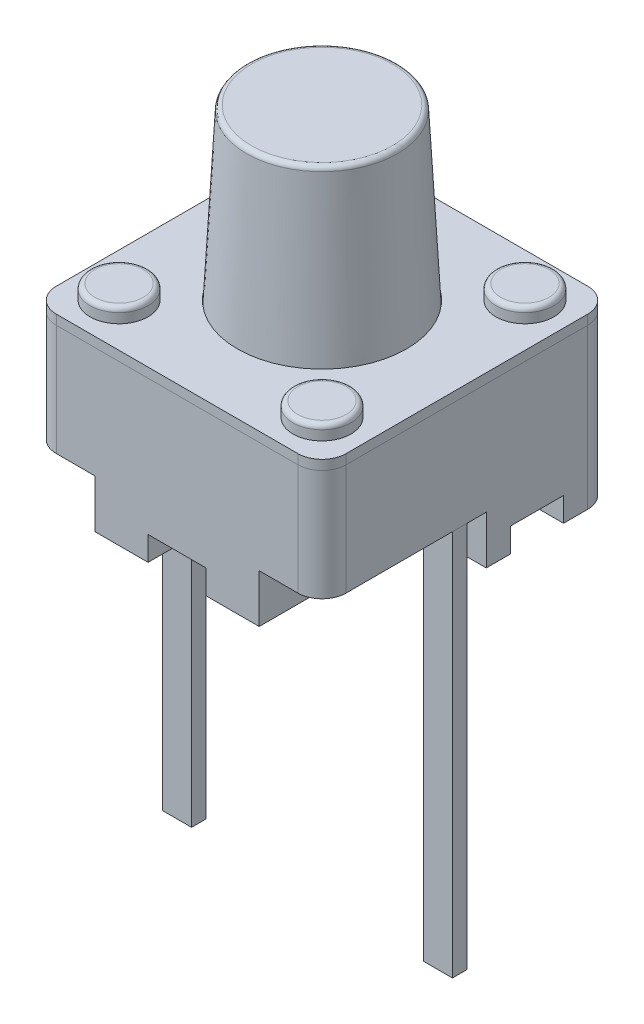
SolidWorks part; units mm, degrees
material "Custom Plastic"
ref_plane "Front Plane" through (0, 0, 0) normal (0, 0, 1) x (1, 0, 0)
ref_plane "Top Plane" through (0, 0, 0) normal (0, 1, 0) x (1, 0, 0)
ref_plane "Right Plane" through (0, 0, 0) normal (1, 0, 0) x (0, 0, -1)
sketch "Sketch1" plane through (0, 0, 0) normal (0, 1, 0) x (1, 0, 0)
  line L0 (-3.2652, 0) -> (3.207, 0) construction
  line L1 (-2.5, 3) -> (2.5, 3)
  line L2 (-3, 2.5) -> (-3, -2.5)
  line L3 (-2.5, -3) -> (2.5, -3)
  line L4 (3, 2.5) -> (3, -2.5)
  line L5 (-3, 3) -> (3, -3) construction
  line L6 (-3, -3) -> (3, 3) construction
  line L7 (0, -3.1905) -> (0, 3.2124) construction
  line L8 (3, 0) -> (2.4, 0)
  line L9 (3, 0) -> (3, -0.3)
  line L10 (3, -0.3) -> (2.4, -0.3)
  line L11 (2.4, 0) -> (2.4, -0.3)
  line L12 (-3, -0.3) -> (-2.4, -0.3)
  line L13 (-2.4, 0) -> (-2.4, -0.3)
  line L14 (-3, 0) -> (-2.4, 0)
  circle A0 centre (2.1, 2.1) radius 0.6
  circle A1 centre (2.1, -2.1) radius 0.6
  circle A2 centre (-2.1, -2.1) radius 0.6
  circle A3 centre (-2.1, 2.1) radius 0.6
  circle A4 centre (0, 0) radius 1.75
  arc A5 (2.5, 3) -> (3, 2.5) centre (2.5, 2.5) cw
  arc A6 (2.5, -3) -> (3, -2.5) centre (2.5, -2.5) ccw
  arc A7 (-3, -2.5) -> (-2.5, -3) centre (-2.5, -2.5) ccw
  arc A8 (-2.5, 3) -> (-3, 2.5) centre (-2.5, 2.5) ccw
  point P0 (0, 0)
  point P1 (0, 0)
  point P9 (0, 0)
  point P18 (0, 0)
  dimension "D1" = 6
  dimension "D2" = 0.9
  dimension "D3" = 1.2
  dimension "D5" = 3.5
  dimension "D6" = 0.5
  dimension "D7" = 0.6
  dimension "D8" = 0.3
  dimension "D4" = 4
extrude "Base" add sketch "Sketch1" along normal blind 3.3 contours L14 L2 L12 L13 | L1 A8 L2 L14 L13 L12 A7 L3 A6 L4 L10 L11 L8 A5 A0 A1 A2 A3 A4 | A3 | A2 | A4 | A1 | L8 L11 L10 L4 | A0 region at (0, 0, -2.9151) region at (-2.7, 0, 0.15) region at (2.7, 0, 0.15) region at (2.1, 0, -2.1) region at (2.1, 0, 2.1) region at (-2.1, 0, 2.1) region at (-2.1, 0, -2.1) region at (0, 0, 0)
extrude "Top Plate" add sketch "Sketch1<3>" along normal blind 0.2 from surface separate body contours L1 A8 L2 L14 L13 L12 A7 L3 A6 L4 L10 L11 L8 A5 A0 A1 A2 A3 A4 | L8 L11 L10 L4 | L14 L2 L12 L13 region at (0, 0, -2.9151) region at (-2.7, 0, 0.15) region at (2.7, 0, 0.15) starting at face at (0, 3.3, 0)
sketch "Sketch1<3>" plane through (0, 0, 0) normal (0, 1, 0) x (1, 0, 0) same geometry as "Sketch1"
extrude "Knobs" add sketch "Sketch1<4>" along normal blind 0.5 from offset 3.3 contours A1 | A2 | A3 | A0 region at (2.1, 0, -2.1) region at (2.1, 0, 2.1) region at (-2.1, 0, 2.1) region at (-2.1, 0, -2.1)
sketch "Sketch1<4>" plane through (0, 0, 0) normal (0, 1, 0) x (1, 0, 0) same geometry as "Sketch1"
extrude "Actuator" add sketch "Sketch1<5>" along normal blind 3.7 draft 3 from surface separate body contours A4 region at (0, 0, 0) starting at face at (-2.1, 3.3, -1.5)
sketch "Sketch1<5>" plane through (0, 0, 0) normal (0, 1, 0) x (1, 0, 0) same geometry as "Sketch1"
sketch "Sketch2" plane through (0, 0, 0) normal (0, -1, 0) x (1, 0, 0)
  line L0 (0, 3) -> (0.6, 3)
  line L1 (0, 3) -> (0, -3) construction
  line L2 (-2.5, 3) -> (2.5, 3) construction
  line L3 (0.6, 3) -> (1.7, 3)
  line L4 (0, -3) -> (0.6, -3)
  line L5 (-1.7, -2) -> (-3, -2)
  line L6 (0.6, -3) -> (0.6, 3)
  line L7 (-1.7, -0.9) -> (-1.7, -2)
  line L8 (-1.7, -0.9) -> (-3, -0.9)
  line L9 (1.7, -0.9) -> (3, -0.9)
  line L10 (1.7, -0.9) -> (1.7, -2)
  line L11 (-3, -0.4) -> (-1.7, -0.4)
  line L12 (-0.6, -3) -> (-0.6, 3)
  line L13 (1.7, 3) -> (1.7, -0.4)
  line L14 (-1.7, 3) -> (-1.7, -0.4)
  line L15 (3, 0) -> (-3, 0) construction
  line L16 (-3, -2.5) -> (-3, 2.5) construction
  line L21 (-2.5, -3) -> (2.5, -3) construction
  line L22 (1.7, -2) -> (3, -2)
  line L23 (3, -2.5) -> (3, 2.5) construction
  line L25 (3, -0.4) -> (1.7, -0.4)
  point P5 (0, 0)
  point P12 (0, 0)
  arc M1 (3, 2.5) -> (2.5, 3) centre (2.5, 2.5) ccw
  line M2 (2.5, 3) -> (-2.5, 3)
  arc M3 (-2.5, 3) -> (-3, 2.5) centre (-2.5, 2.5) ccw
  line M4 (-3, 2.5) -> (-3, -2.5)
  line M6 (-2.5, -3) -> (2.5, -3)
  line M8 (3, -2.5) -> (3, 2.5)
  dimension "D1" = 0.6
  dimension "D2" = 1.7
  dimension "D3" = 0.4
  dimension "D4" = 1
  dimension "D6" = 0.5
extrude "Base Leg Cutout" cut sketch "Sketch2" against normal blind 1 from surface contours L14 L11 M2 M3 M4 | L25 L13 M8 M1 M2 region at (2.3434, 0, 1.2805) region at (-2.3434, 0, 1.2805) starting at face at (0, 0, 0)
extrude "Base Shallow Cutout" cut sketch "Sketch2<3>" against normal blind 0.5 contours L1 L12 M2 M6 | L10 L22 L9 M8 | L7 L8 L5 M4 region at (2.35, 0, -1.45) region at (-2.35, 0, -1.45) region at (0, 0, 0)
sketch "Sketch2<3>" plane through (0, 0, 0) normal (0, -1, 0) x (1, 0, 0) same geometry as "Sketch2"
extrude "Pins" add sketch "Sketch1<7>" against normal blind 8 from offset 1 separate body contours L14 L2 L12 L13 | L8 L11 L10 L4 region at (-2.7, 0, 0.15) region at (2.7, 0, 0.15)
sketch "Sketch1<7>" plane through (0, 0, 0) normal (0, 1, 0) x (1, 0, 0) same geometry as "Sketch1"
fillet "Fillet1" radius 0.1 1 edges at (0, 7, 1.5561)
fillet "Fillet2" radius 0.1 4 edges at (-2.1, 3.8, -1.5) (2.1, 3.8, -1.5) (-2.1, 3.8, 2.7) (2.1, 3.8, 2.7)
